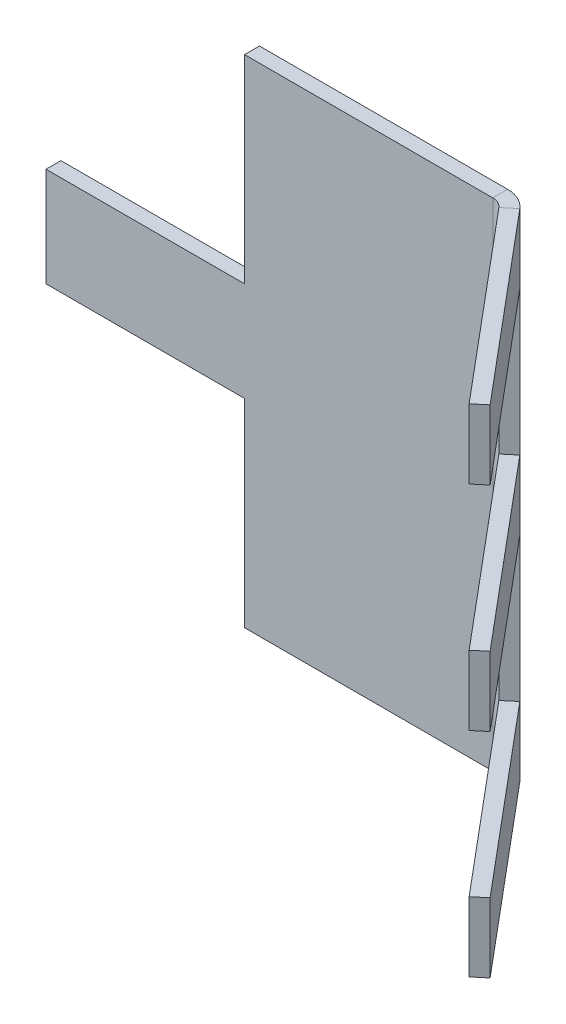
SolidWorks part; units mm, degrees
note: The reader was unsure of these and kept them because the rebuilt part matched: flange length of "Edge-Flange2".
ref_plane "Front Plane" through (0, 0, 0) normal (0, 0, 1) x (1, 0, 0)
ref_plane "Top Plane" through (0, 0, 0) normal (0, 1, 0) x (1, 0, 0)
ref_plane "Right Plane" through (0, 0, 0) normal (1, 0, 0) x (0, 0, -1)
sketch "Sketch1" plane through (0, 0, 0) normal (0, 0, 1) x (1, 0, 0)
  line L1 (-36.5711, 26.9639) -> (13.4289, 26.9639)
  line L2 (-36.5711, 26.9639) -> (-36.5711, -73.0361)
  line L3 (-36.5711, -73.0361) -> (13.4289, -73.0361)
  line L4 (13.4289, 26.9639) -> (13.4289, -73.0361)
  dimension "D1" = 50
  dimension "D2" = 100
base flange "Base-Flange1" sketch "Sketch1" thickness 3 reverse thickness direction no parameters "D1"=3
edge flange "Edge-Flange2" sketch "Sketch11" flange angle 130 flange length 50 flange position bend outside bend radius 3 thickness 3 relief rectangular parameters "D6"=10
sketch "Sketch11" plane through (13.4289, 0, 0) normal (0.766, 0, -0.6428) x (0, 1, 0)
  line L2 (-73.0361, 0) -> (-73.0361, 50)
  line L3 (-73.0361, 50) -> (26.9639, 50)
  line L4 (26.9639, 50) -> (26.9639, 0)
  line L5 (-73.0361, 0) -> (26.9639, 0) construction
  line L6 (-73.0361, 0) -> (26.9639, 0)
bend "EdgeBend2" bend radius 3 bend angle 50 parameters "D5"=1
sketch "Sketch12" plane through (8.7013, 0, -7.3013) normal (-0.766, 0, 0.6428) x (0.6428, 0, 0.766)
  line L0 (59.5311, 26.9639) -> (59.5311, -73.0361) construction
  line L1 (59.5311, 12.9639) -> (10.93, 12.9639)
  line L2 (59.5311, 12.9639) -> (59.5311, -16.0361)
  line L3 (59.5311, -16.0361) -> (10.93, -16.0361)
  line L4 (10.93, 12.9639) -> (10.93, -16.0361)
  line L5 (10.93, -73.0361) -> (10.93, 26.9639) construction
  line L6 (10.93, 26.9639) -> (59.5311, 26.9639) construction
  dimension "D1" = 29
  dimension "D2" = 14
extrude "Cut-Extrude1" cut sketch "Sketch12" against normal blind 29 normal cut yes
sketch "Sketch13" plane through (8.7013, 0, -7.3013) normal (-0.766, 0, 0.6428) x (0.6428, 0, 0.766)
  line L0 (59.5311, -16.0361) -> (59.5311, -73.0361) construction
  line L1 (59.5311, -59.0361) -> (10.93, -59.0361)
  line L2 (59.5311, -59.0361) -> (59.5311, -30.0361)
  line L3 (59.5311, -30.0361) -> (10.93, -30.0361)
  line L4 (10.93, -59.0361) -> (10.93, -30.0361)
  line L5 (10.93, -73.0361) -> (10.93, -16.0361) construction
  line L6 (59.5311, -73.0361) -> (10.93, -73.0361) construction
  dimension "D1" = 29
  dimension "D2" = 14
extrude "Cut-Extrude2" cut sketch "Sketch13" against normal blind 29 normal cut yes
sketch "Sketch14" plane through (0, 0, 0) normal (0, 0, 1) x (1, 0, 0)
  line L0 (-11.5711, 26.9639) -> (-11.5711, -73.0361) construction
  line L1 (13.4289, 26.9639) -> (-36.5711, 26.9639) construction
  line L2 (-36.5711, -73.0361) -> (13.4289, -73.0361) construction
  line L3 (-11.5711, -73.0361) -> (-36.5711, -23.0361) construction
  line L4 (-36.5711, 26.9639) -> (-36.5711, -73.0361) construction
  line L5 (-36.5711, -23.0361) -> (13.4289, -23.0361) construction
  line L6 (13.4289, -73.0361) -> (13.4289, 26.9639) construction
  line L8 (3.4289, -33.0361) -> (-76.5711, -33.0361)
  line L9 (3.4289, -33.0361) -> (3.4289, -13.0361)
  line L10 (3.4289, -13.0361) -> (-76.5711, -13.0361)
  line L11 (-76.5711, -33.0361) -> (-76.5711, -13.0361)
  line L12 (3.4289, -33.0361) -> (-76.5711, -13.0361) construction
  line L13 (3.4289, -13.0361) -> (-76.5711, -33.0361) construction
  dimension "D1" = 20
  dimension "D2" = 80
base flange "Tab1" sketch "Sketch14" thickness 3 reverse thickness direction no parameters "D1"=3
sketch "Bend-Lines1" plane through (0, 0, 0) normal (0, 1, 0) x (1, 0, 0)
sketch "Bounding-Box1" plane through (0, 0, 0) normal (0, 1, 0) x (1, 0, 0)
sheet metal parameters "Sheet-Metal1" thickness 3 parameters "D1"=3
flat pattern "Flat-Pattern1" [suppressed]
sketch "Bend-Lines2" plane through (0, 0, 0) normal (0, 1, 0) x (1, 0, 0)
sketch "Bounding-Box2" [suppressed] plane through (0, 0, 0) normal (0, 1, 0) x (1, 0, 0)
sheet metal parameters "Sheet-Metal3" thickness 3 parameters "D1"=3
flat pattern "Flat-Pattern1" [suppressed]
sketch "Bend-Lines2" plane through (0, 0, 0) normal (0, 1, 0) x (1, 0, 0)
sketch "Bounding-Box2" [suppressed] plane through (0, 0, 0) normal (0, 1, 0) x (1, 0, 0)
bend of the flat pattern "Flatten-<EdgeBend2>1"
sheet metal parameters "Sheet-Metal4" thickness 3 parameters "D1"=3
flat pattern "Flat-Pattern1" [suppressed]
sketch "Bend-Lines2" plane through (0, 0, 0) normal (0, 1, 0) x (1, 0, 0)
sketch "Bounding-Box2" [suppressed] plane through (0, 0, 0) normal (0, 1, 0) x (1, 0, 0)
bend of the flat pattern "Flatten-<EdgeBend2>1"
sheet metal parameters "Sheet-Metal5" thickness 3 parameters "D1"=3
flat pattern "Flat-Pattern1" [suppressed]
sketch "Bend-Lines2" plane through (0, 0, 0) normal (0, 1, 0) x (1, 0, 0)
sketch "Bounding-Box2" [suppressed] plane through (0, 0, 0) normal (0, 1, 0) x (1, 0, 0)
bend of the flat pattern "Flatten-<EdgeBend2>1"
sheet metal parameters "Sheet-Metal6" thickness 3 parameters "D1"=3
flat pattern "Flat-Pattern6" [suppressed]
sketch "Bend-Lines3" plane through (0, 0, 0) normal (0, 1, 0) x (1, 0, 0)
sketch "Bounding-Box3" [suppressed] plane through (0, 0, 0) normal (0, 1, 0) x (1, 0, 0)
bend of the flat pattern "Flatten-<EdgeBend2>2"
